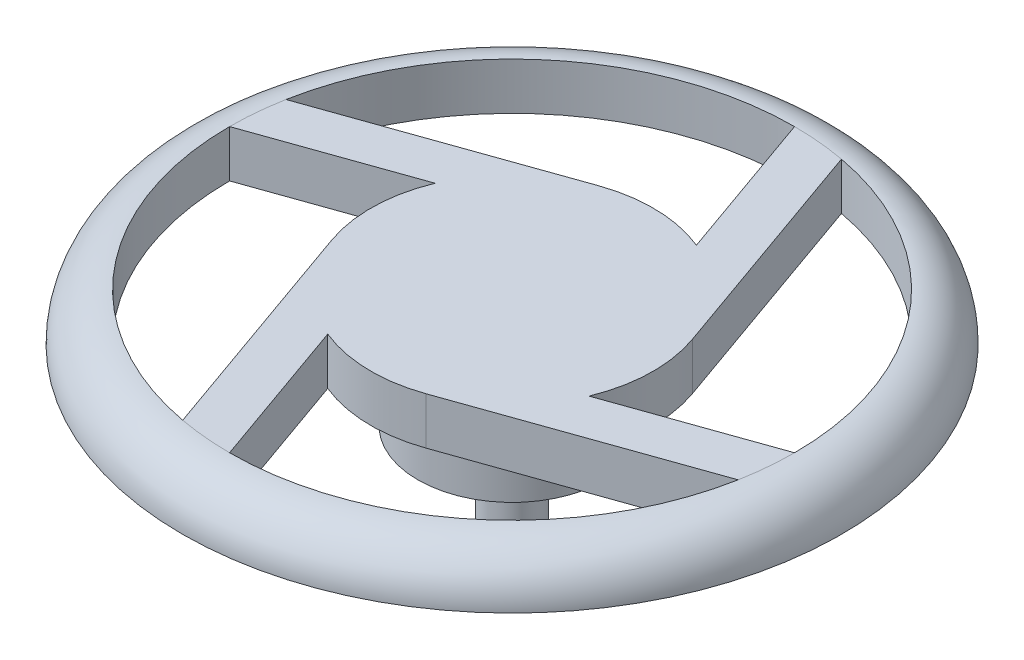
SolidWorks part; units mm, degrees
material "Gray Cast Iron"
ref_plane "Front Plane" through (0, 0, 0) normal (0, 0, 1) x (1, 0, 0)
ref_plane "Top Plane" through (0, 0, 0) normal (0, 1, 0) x (1, 0, 0)
ref_plane "Right Plane" through (0, 0, 0) normal (1, 0, 0) x (0, 0, -1)
sketch "Sketch2" plane through (0, 0, 0) normal (0, 1, 0) x (1, 0, 0)
  circle A0 centre (0, 0) radius 60
  circle A1 centre (0, 0) radius 70
  dimension "D1" = 120
  dimension "D2" = 10
sketch "Sketch5" plane through (0, 0, 0) normal (0, 1, 0) x (1, 0, 0)
  line L0 (6.6667, -18.8562) -> (60, 0)
  circle A0 centre (0, 0) radius 20
  circle A1 centre (0, 0) radius 60 construction
extrude "Extrude-Thin2" add sketch "Sketch5" along normal blind 10 thin contours A0 | L0
extrude "Boss-Extrude3" add sketch "Sketch2" along normal blind 10
pattern_circular "CirPattern1" count 4 over 360 about axis through (0, 0, 0) along (0, 1, 0) of "Extrude-Thin2"
sketch "Sketch6" plane through (0, 10, 0) normal (0, 1, 0) x (1, 0, 0)
  circle A0 centre (0, 0) radius 20
  circle A1 centre (0, 0) radius 70
  circle A2 centre (0, 0) radius 70
  circle A3 centre (0, 0) radius 20
  point P1 (0, 0)
  dimension "D2" = 40
  dimension "D1" = 0
extrude "Boss-Extrude4" add sketch "Sketch6" against normal blind 25
fillet "Fillet2" radius 10 1 edges at (0, 10, 70)
sketch "Sketch7" plane through (0, -15, 0) normal (0, -1, 0) x (1, 0, 0)
  circle A0 centre (0, 0) radius 5.5
  dimension "D1" = 11
extrude "Boss-Extrude5" add sketch "Sketch7" along normal blind 22
